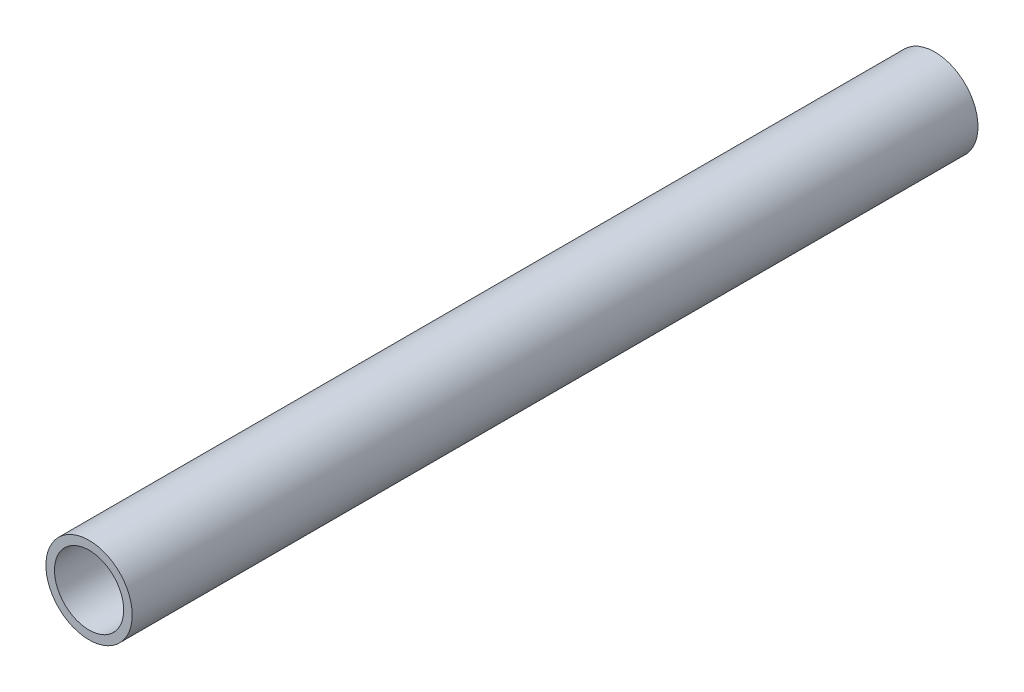
SolidWorks part; units mm, degrees
ref_plane "Front Plane" through (0, 0, 0) normal (0, 0, 1) x (1, 0, 0)
ref_plane "Top Plane" through (0, 0, 0) normal (0, 1, 0) x (1, 0, 0)
ref_plane "Right Plane" through (0, 0, 0) normal (1, 0, 0) x (0, 0, -1)
sketch "Sketch1" plane through (0, 0, 0) normal (0, 0, 1) x (1, 0, 0)
  circle A0 centre (0, 0) radius 4.05
  dimension "D1" = 8.1
extrude "Extrude-Thin1" add sketch "Sketch1" along normal blind 99 thin thin type one direction wall 1
